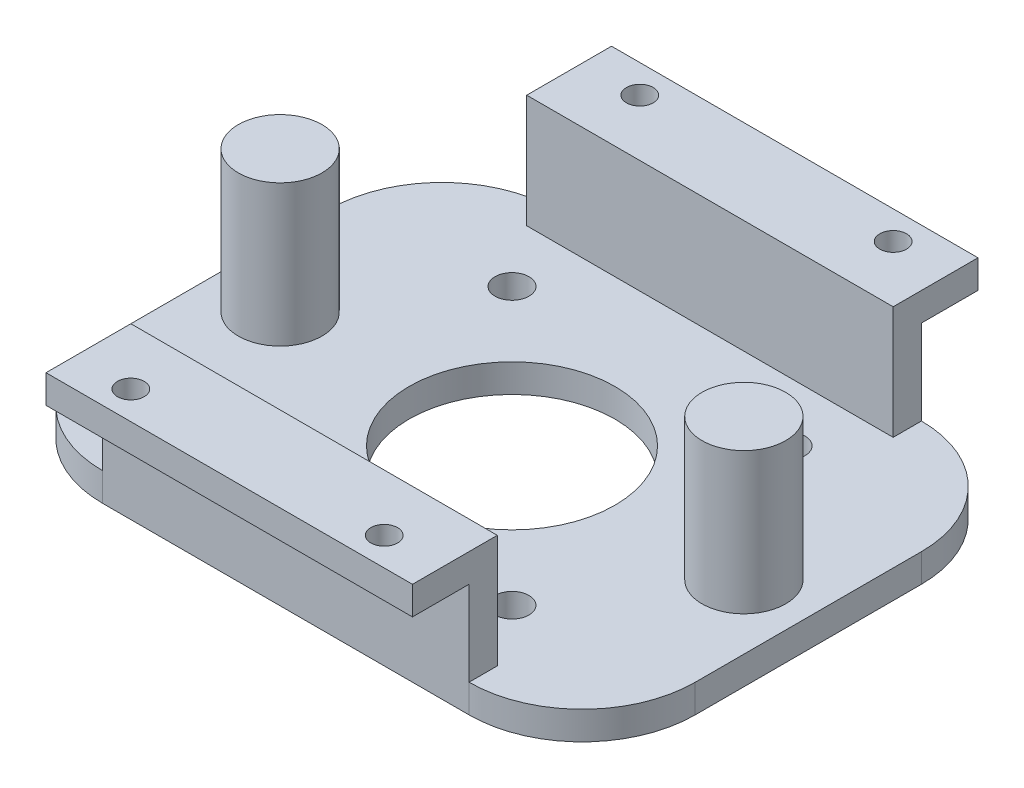
SolidWorks part; units mm, degrees
ref_plane "Front Plane" through (0, 0, 0) normal (0, 0, 1) x (1, 0, 0)
ref_plane "Top Plane" through (0, 0, 0) normal (0, 1, 0) x (1, 0, 0)
ref_plane "Right Plane" through (0, 0, 0) normal (1, 0, 0) x (0, 0, -1)
sketch "Sketch1" plane through (0, 0, 0) normal (0, 1, 0) x (1, 0, 0)
  line L5 (-15.5, -15.5) -> (15.5, -15.5) construction
  line L6 (-15.5, -15.5) -> (-15.5, 15.5) construction
  line L7 (-15.5, 15.5) -> (15.5, 15.5) construction
  line L8 (15.5, -15.5) -> (15.5, 15.5) construction
  line L9 (-15.5, -15.5) -> (15.5, 15.5) construction
  line L10 (-15.5, 15.5) -> (15.5, -15.5) construction
  line L11 (-20.574, -25.4) -> (20.574, -25.4)
  line L12 (-20.574, -25.4) -> (-20.574, 25.4)
  line L13 (-20.574, 25.4) -> (20.574, 25.4)
  line L14 (20.574, -25.4) -> (20.574, 25.4)
  line L15 (-20.574, -25.4) -> (20.574, 25.4) construction
  line L16 (-20.574, 25.4) -> (20.574, -25.4) construction
  circle A0 centre (0, 0) radius 11.557
  circle A1 centre (-15.5, 15.5) radius 1.905
  circle A2 centre (15.5, 15.5) radius 1.905
  circle A3 centre (15.5, -15.5) radius 1.905
  circle A4 centre (-15.5, -15.5) radius 1.905
  point P0 (0, 0)
  point P18 (0, 0)
  dimension "D2" = 23.114
  dimension "D3" = 3.81
  dimension "D1" = 31
  dimension "D5" = 50.8
  dimension "D6" = 41.148
  dimension "D4" = 4
extrude "Boss-Extrude1" add sketch "Sketch1" along normal blind 3.175
sketch "Sketch2" plane through (0, 3.175, 0) normal (0, 1, 0) x (1, 0, 0)
  line L0 (20.574, -25.4) -> (20.574, 25.4) construction
  line L1 (-20.574, -25.4) -> (20.574, -25.4)
  line L2 (-20.574, -25.4) -> (-20.574, -22.225)
  line L3 (-20.574, -22.225) -> (20.574, -22.225)
  line L4 (20.574, -25.4) -> (20.574, -22.225)
  line L5 (-20.574, 0) -> (20.574, 0) construction
  line L6 (-20.574, 25.4) -> (-20.574, -25.4) construction
  line L7 (20.574, 25.4) -> (20.574, 22.225)
  line L8 (-20.574, 22.225) -> (20.574, 22.225)
  line L9 (-20.574, 25.4) -> (-20.574, 22.225)
  line L10 (-20.574, 25.4) -> (20.574, 25.4)
  dimension "D1" = 3.175
extrude "Boss-Extrude2" add sketch "Sketch2" along normal blind 12.7
sketch "Sketch3" plane through (0, 0, -25.4) normal (0, 0, -1) x (-1, 0, 0)
  line L0 (-20.574, 15.875) -> (-20.574, 12.7)
  line L1 (-20.574, 12.7) -> (20.574, 12.7)
  line L2 (20.574, 15.875) -> (20.574, 0) construction
  line L3 (20.574, 12.7) -> (20.574, 15.875)
  line L4 (20.574, 15.875) -> (-20.574, 15.875)
  dimension "D1" = 3.175
extrude "Boss-Extrude3" add sketch "Sketch3" along normal blind 6.35
sketch "Sketch4" plane through (0, 0, 25.4) normal (0, 0, 1) x (1, 0, 0)
  line L0 (-20.574, 15.875) -> (-20.574, 12.7)
  line L1 (-20.574, 12.7) -> (20.574, 12.7)
  line L2 (20.574, 15.875) -> (20.574, 0) construction
  line L3 (20.574, 12.7) -> (20.574, 15.875)
  line L4 (20.574, 15.875) -> (-20.574, 15.875)
  dimension "D1" = 3.175
extrude "Boss-Extrude4" add sketch "Sketch4" along normal blind 6.35
sketch "Sketch5" plane through (0, 12.7, 0) normal (0, -1, 0) x (1, 0, 0)
  line L0 (-20.574, 28.575) -> (-14.224, 28.575) construction
  line L1 (-20.574, 31.75) -> (-20.574, 25.4) construction
  line L2 (0, 0) -> (0, 4.866) construction
  line L3 (0, 0) -> (-6.8218, 0) construction
  circle A0 centre (-14.224, 28.575) radius 1.5
  circle A1 centre (14.224, 28.575) radius 1.5
  circle A2 centre (14.224, -28.575) radius 1.5
  circle A3 centre (-14.224, -28.575) radius 1.5
  dimension "D2" = 3
  dimension "D1" = 6.35
extrude "Cut-Extrude1" cut sketch "Sketch5" against normal blind 6.35
sketch "Sketch6" plane through (-20.574, 0, 0) normal (-1, 0, 0) x (0, 0, 1)
  line L0 (-25.4, 0) -> (25.4, 0) construction
  line L1 (-22.225, 3.175) -> (22.225, 3.175) construction
  line L2 (-25.4, 0) -> (25.4, 0)
  line L3 (-22.225, 3.175) -> (22.225, 3.175)
  line L4 (-22.225, 3.175) -> (-25.4, 3.175)
  line L5 (-25.4, 12.7) -> (-25.4, 0) construction
  line L6 (-25.4, 3.175) -> (-25.4, 0)
  line L7 (22.225, 3.175) -> (25.4, 3.175)
  line L8 (25.4, 12.7) -> (25.4, 0) construction
  line L9 (25.4, 3.175) -> (25.4, 0)
extrude "Boss-Extrude5" add sketch "Sketch6" along normal blind 12.7
sketch "Sketch7" plane through (20.574, 0, 0) normal (1, 0, 0) x (0, 0, -1)
  line L0 (-25.4, 0) -> (25.4, 0) construction
  line L1 (-22.225, 3.175) -> (22.225, 3.175) construction
  line L2 (-25.4, 0) -> (25.4, 0)
  line L3 (-22.225, 3.175) -> (22.225, 3.175)
  line L4 (-22.225, 3.175) -> (-25.4, 3.175)
  line L5 (-25.4, 3.175) -> (-25.4, 0)
  line L6 (22.225, 3.175) -> (25.4, 3.175)
  line L7 (25.4, 3.175) -> (25.4, 0)
extrude "Boss-Extrude6" add sketch "Sketch7" along normal blind 12.7
sketch "Sketch8" plane through (0, 0, 0) normal (0, -1, 0) x (1, 0, 0)
  line L0 (0, -31.75) -> (0, 31.75) construction
  line L1 (-20.574, 31.75) -> (20.574, 31.75) construction
  circle A0 centre (0, 0) radius 7.62 construction
  circle A1 centre (-26.035, 0) radius 18.415 construction
  circle A2 centre (-26.035, 0) radius 4.699
  circle A3 centre (26.035, 0) radius 4.699
  point P11 (0, 0)
  dimension "D1" = 15.24
  dimension "D2" = 36.83
  dimension "D3" = 9.398
extrude "Boss-Extrude7" add sketch "Sketch8" against normal blind 19.05
fillet "Fillet1" radius 12.7 4 edges at (-33.274, 1.5875, -25.4) (33.274, 1.5875, -25.4) (33.274, 1.5875, 25.4) (-33.274, 1.5875, 25.4)
